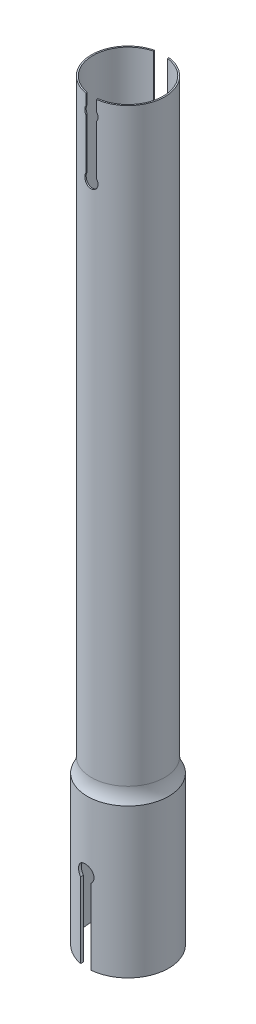
SolidWorks part; units mm, degrees
material "Aleación 1060"
ref_plane "Alzado" through (0, 0, 0) normal (0, 0, 1) x (1, 0, 0)
ref_plane "Planta" through (0, 0, 0) normal (0, 1, 0) x (1, 0, 0)
ref_plane "Vista lateral" through (0, 0, 0) normal (1, 0, 0) x (0, 0, -1)
sketch "Croquis2" plane through (0, 0, 0) normal (0, 1, 0) x (1, 0, 0)
  circle A0 centre (0, 0) radius 15
  dimension "D1" = 30
extrude "Saliente-Extruir2" add sketch "Croquis2" along normal blind 55
sketch "Croquis3" plane through (0, 0, 0) normal (0, 0, 1) x (1, 0, 0)
  line L0 (0, 0) -> (0, 23.7954) construction
  line L1 (0, 23.7954) -> (15, 0) construction
  line L3 (-2.7403, 0) -> (1.2597, 0)
  line L4 (-2.7403, 0) -> (-2.7403, 27.7639)
  line L6 (1.2597, 0) -> (1.2597, 27.7639)
  arc A0 (1.2597, 27.7639) -> (-2.7403, 27.7639) centre (-0.7403, 30) ccw
  dimension "D3" = 6
extrude "Cortar-Extruir1" cut sketch "Croquis3" against normal mid plane 55
sketch "Croquis6" plane through (0, 0, 0) normal (0, 1, 0) x (1, 0, 0)
  circle A0 centre (0, 0) radius 14
  circle A1 centre (0, 0) radius 15 construction
  dimension "D1" = 1
extrude "Cortar-Extruir3" cut sketch "Croquis6" along normal blind 54
sketch "Croquis7" plane through (0, 55, 0) normal (0, 1, 0) x (1, 0, 0)
  circle A0 centre (0, 0) radius 13.5
  dimension "D1" = 27
extrude "Saliente-Extruir4" add sketch "Croquis7" along normal blind 223
sketch "Croquis8" plane through (0, 0, 0) normal (0, 0, 1) x (1, 0, 0)
  line L0 (-13.5, 278) -> (-13.5, 196) construction
  line L1 (-13.5, 278) -> (-13.5, 55) construction
  line L3 (-13.5, 278) -> (13.5, 278) construction
  line L4 (13.5, 278) -> (-13.5, 278) construction
  line L5 (13.5, 278) -> (13.5, 196) construction
  line L6 (13.5, 55) -> (13.5, 278) construction
  line L7 (13.5, 196) -> (-13.5, 196) construction
  line L9 (1.7394, 278) -> (-3.2606, 278)
  line L10 (1.7394, 278) -> (1.7394, 245.3301)
  line L12 (-3.2606, 278) -> (-3.2606, 245.3301)
  arc A0 (-3.2606, 245.3301) -> (1.7394, 245.3301) centre (-0.7606, 241) ccw
  dimension "D4" = 10
  dimension "D1" = 82
extrude "Cortar-Extruir5" cut sketch "Croquis8" against normal up to next contours A0 L10 L9 L12
sketch "Croquis9" plane through (0, 0, 0) normal (0, 0, 1) x (1, 0, 0)
  circle A0 centre (0, 209) radius 3.5
  arc A1 (-3.2606, 245.3301) -> (1.7394, 245.3301) centre (-0.7606, 241) ccw construction
  dimension "D1" = 32
  dimension "D2" = 7
extrude "Cortar-Extruir6" cut sketch "Croquis9" against normal blind 23
sketch "Croquis10" plane through (0, 0, 0) normal (0, 0, -1) x (-1, 0, 0)
  line L0 (2.2606, 271.0191) -> (2.2606, 252.4809)
  line L2 (0, 248.5122) -> (0, 247.8531) construction
  line L3 (-1.7394, 278) -> (2.2606, 278)
  line L4 (-1.7394, 278) -> (-1.7394, 274.0187)
  line L6 (2.2606, 278) -> (2.2606, 273.9809)
  line L7 (-1.7394, 270.9813) -> (-1.7394, 252.5187)
  arc A0 (2.2606, 271.0191) -> (2.2606, 273.9809) centre (0.2465, 272.5) ccw
  arc A1 (-1.7394, 252.5187) -> (2.2606, 252.4809) centre (0.2465, 251) ccw
  arc A2 (-1.7394, 274.0187) -> (-1.7394, 270.9813) centre (0.2465, 272.5) ccw
  dimension "D3" = 5
  dimension "D4" = 5.5
  dimension "D5" = 5
extrude "Cortar-Extruir7" cut sketch "Croquis10" against normal blind 23
sketch "Croquis11" plane through (0, 0, 0) normal (0, 1, 0) x (1, 0, 0)
  circle A0 centre (0, 0) radius 13
  dimension "D1" = 26
extrude "Cortar-Extruir8" cut sketch "Croquis11" along normal blind 291
fillet "Redondeo1" radius 10 1 edges at (0, 55, 13.5)
sketch3d "Croquis3D1"
  point P0 (-0.3405, 30.0746, 13.9959)
ref_plane "Plano1" through (0, 0, 13.9959) normal (0, 0, -1) x (-1, 0, 0)
